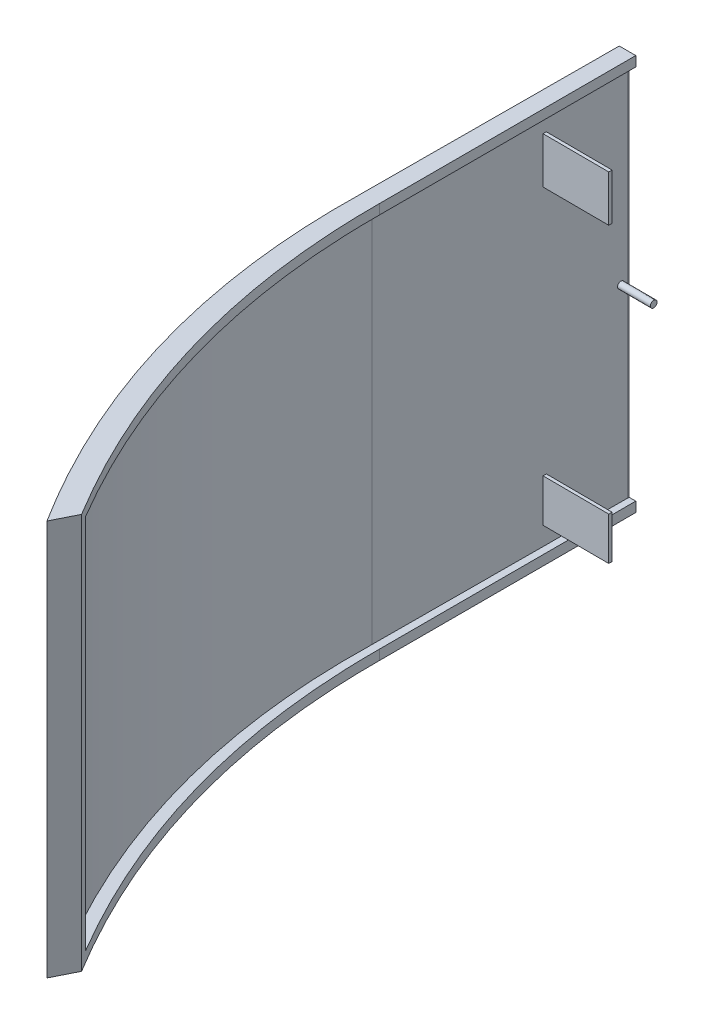
SolidWorks part; units mm, degrees
material "PET"
ref_plane "Front" through (0, 0, 0) normal (0, 0, 1) x (1, 0, 0)
ref_plane "Top" through (0, 0, 0) normal (0, 1, 0) x (1, 0, 0)
ref_plane "Right" through (0, 0, 0) normal (1, 0, 0) x (0, 0, -1)
sketch "Sketch1" plane through (0, 0, 0) normal (0, 1, 0) x (1, 0, 0)
  line L0 (-74.1629, 98.0421) -> (-73.8322, 178.2204)
  line L5 (-73.8322, 178.2204) -> (-68.8334, 178.2204)
  line L6 (-68.8334, 178.2204) -> (-68.8334, 98.0421)
  line L8 (-32.3787, -28.7863) -> (-35.8787, -35.7842)
  spline S0 degree 2 poles (-74.1629, 98.0421) (-75.7638, 27.7521) (-35.8787, -35.7842) knots 0 0 0 1 1 1
  spline S1 degree 2 poles (-68.8334, 98.0421) (-69.1894, 31.8601) (-32.3787, -28.7863) knots 0 0 0 1 1 1
  dimension "D2" = 3.5
extrude "Boss-Extrude1" add sketch "Sketch1" along normal blind 120
shell "Shell4" thickness 3 removed face at (-68.8334, 60, -138.1313) removed face at (-41.4924, 60, -2.9208)
sketch "Sketch12" plane through (-68.8334, 0, 0) normal (1, 0, 0) x (0, 0, -1)
  line L0 (175.2204, 117) -> (178.7194, 117)
  line L1 (175.2204, 117) -> (175.2204, 3)
  line L2 (175.2204, 3) -> (178.7194, 3)
  line L3 (178.7194, 3) -> (178.7194, 117)
extrude "Cut-Extrude5" cut sketch "Sketch12" against normal blind 2
sketch "Sketch9" plane through (-71.5661, 0, -0.2952) normal (1, 0, 0.0041) x (0.0041, 0, -1)
  circle A0 centre (172.9255, 60) radius 1.0045
extrude "Boss-Extrude5" add sketch "Sketch9" along normal blind 10
sketch "Sketch13" plane through (-68.8334, 0, 0) normal (1, 0, 0) x (0, 0, -1)
  line L0 (178.2204, 120) -> (175.719, 120)
  line L1 (98.0421, 120) -> (178.2204, 120) construction
  line L2 (175.719, 120) -> (175.719, 0)
  line L3 (98.0421, 0) -> (178.2204, 0) construction
  line L4 (175.719, 0) -> (178.7214, 0)
  line L5 (178.7214, 0) -> (178.7214, 120)
  line L6 (178.7214, 120) -> (178.2204, 120)
extrude "Cut-Extrude6" cut sketch "Sketch13" against normal blind 10
sketch "Sketch14" plane through (-71.5661, 0, -0.2952) normal (1, 0, 0.0041) x (0.0041, 0, -1)
  line L0 (149.4206, 15.0837) -> (149.4206, 9.5895)
  line L1 (175.4253, 117) -> (175.4253, 3) construction
  line L2 (149.4206, 9.5895) -> (149.4206, 21.5767)
  line L3 (149.4206, 15.0837) -> (149.4206, 9.5895)
  line L4 (149.4206, 21.5767) -> (150.4206, 21.5767)
  line L5 (149.4206, 9.5895) -> (149.4206, 15.0837)
  line L6 (150.4206, 15.0837) -> (175.4253, 15.0837)
  line L7 (149.4206, 15.0837) -> (149.4206, 21.5767)
  line L8 (149.4206, 111.422) -> (149.4206, 103.9172)
  line L9 (150.4206, 103.9172) -> (175.4253, 103.9172)
  line L10 (149.4206, 103.9172) -> (149.4206, 111.422)
  line L11 (149.4206, 103.9172) -> (149.4206, 97.4154)
  line L12 (149.4206, 97.4154) -> (149.4206, 111.422)
  line L14 (150.4206, 97.4154) -> (150.4206, 111.422)
  line L15 (150.4206, 111.422) -> (149.4206, 111.422)
  line L16 (149.4206, 9.5895) -> (149.4206, 8.5928)
  line L17 (149.4206, 8.5928) -> (150.4206, 8.5928)
  line L18 (150.4206, 8.5928) -> (150.4206, 9.5895)
  line L20 (150.4206, 9.5895) -> (150.4206, 21.5767)
  line L21 (149.4206, 97.4154) -> (150.4206, 97.4154)
extrude "Boss-Extrude6" add sketch "Sketch14" along normal blind 20 contours L20 L2 L0 | L14 L15 L8 L11 region at (-70.9477, 15.0848, -150.2146) region at (-70.9477, 104.4187, -150.2146)
